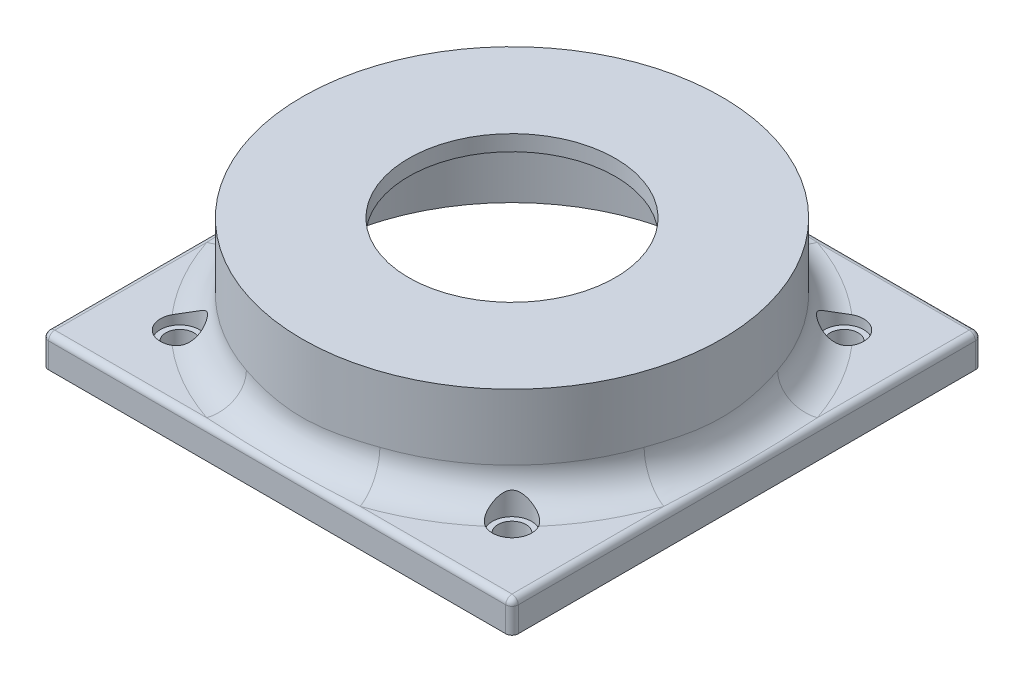
SolidWorks part; units mm, degrees
ref_plane "Спереди" through (0, 0, 0) normal (0, 0, 1) x (1, 0, 0)
ref_plane "Сверху" through (0, 0, 0) normal (0, 1, 0) x (1, 0, 0)
ref_plane "Справа" through (0, 0, 0) normal (1, 0, 0) x (0, 0, -1)
sketch "Эскиз1" plane through (0, 0, 0) normal (0, 1, 0) x (1, 0, 0)
  line L0 (0, 0) -> (53.033, 53.033) construction
  line L5 (75, -75) -> (-75, -75)
  line L6 (75, -75) -> (75, 75)
  line L7 (75, 75) -> (-75, 75)
  line L8 (-75, -75) -> (-75, 75)
  line L9 (75, -75) -> (-75, 75) construction
  line L10 (75, 75) -> (-75, -75) construction
  circle A2 centre (0, 0) radius 75 construction
  circle A3 centre (53.033, 53.033) radius 4.5
  circle A4 centre (0, 0) radius 75 construction
  circle A5 centre (53.033, -53.033) radius 4.5
  circle A6 centre (0, 0) radius 75 construction
  circle A7 centre (-53.033, -53.033) radius 4.5
  circle A8 centre (0, 0) radius 75 construction
  circle A9 centre (-53.033, 53.033) radius 4.5
  point P0 (0, 0)
  dimension "D3" = 150
  dimension "D4" = 9
  dimension "D1" = 150
  dimension "D2" = 150
  dimension "D5" = 4
extrude "Бобышка-Вытянуть1" add sketch "Эскиз1" along normal blind 10
fillet "Скругление1" radius 2 4 edges at (-75, 5, -75) (75, 5, -75) (-75, 5, 75) (75, 5, 75)
fillet "Скругление2" radius 2 8 edges at (-74.4142, 10, -74.4142) (74.4142, 10, -74.4142) (74.4142, 10, 74.4142) (-74.4142, 10, 74.4142) (0, 10, 75) (75, 10, 0) (0, 10, -75) (-75, 10, 0)
sketch "Эскиз3" plane through (0, 10, 0) normal (0, 1, 0) x (1, 0, 0)
  line L0 (0, -75) -> (0, 75)
  line L1 (-73, 75) -> (73, 75) construction
  circle A1 centre (-53.033, 53.033) radius 6.25
  circle A2 centre (-53.033, -53.033) radius 6.25
  circle A3 centre (53.033, -53.033) radius 6.25
  circle A4 centre (53.033, 53.033) radius 6.25
  point P14 (0, 0)
  dimension "D1" = 150
  dimension "D2" = 12.5
  dimension "D3" = 12.5
extrude "Вырез-Вытянуть1" cut sketch "Эскиз3" against normal blind 3 contours A3 | A2 | A1 | A4
sketch "Эскиз4" plane through (0, 10, 0) normal (0, 1, 0) x (1, 0, 0)
  circle A0 centre (0, 0) radius 67
  dimension "D1" = 134
extrude "Бобышка-Вытянуть4" add sketch "Эскиз4" along normal blind 31 contours A0
fillet "Скругление5" radius 10 1 edges at (0, 10, 67)
sketch "Эскиз5" plane through (0, 41, 0) normal (0, 1, 0) x (1, 0, 0)
  circle A0 centre (0, 0) radius 64
  circle A1 centre (0, 0) radius 33
  dimension "D1" = 128
  dimension "D2" = 66
extrude "Вырез-Вытянуть4" cut sketch "Эскиз5" against normal blind 74 contours A1
sketch "Эскиз10" plane through (0, 0, 0) normal (0, -1, 0) x (1, 0, 0)
  circle A0 centre (0, 0) radius 64
  dimension "D1" = 128
extrude "Вырез-Вытянуть7" cut sketch "Эскиз10" against normal blind 36
equation "\"D2@Эскиз1\"=\"D1@Эскиз1\""
equation "\"D3@Эскиз1\"=\"D1@Эскиз1\""
equation "\"D3@Эскиз3\"=\"D2@Эскиз3\""
equation "\"D1@Вырез-Вытянуть7\"=(\"D1@Бобышка-Вытянуть1\"+\"D1@Бобышка-Вытянуть4\")-5мм"
